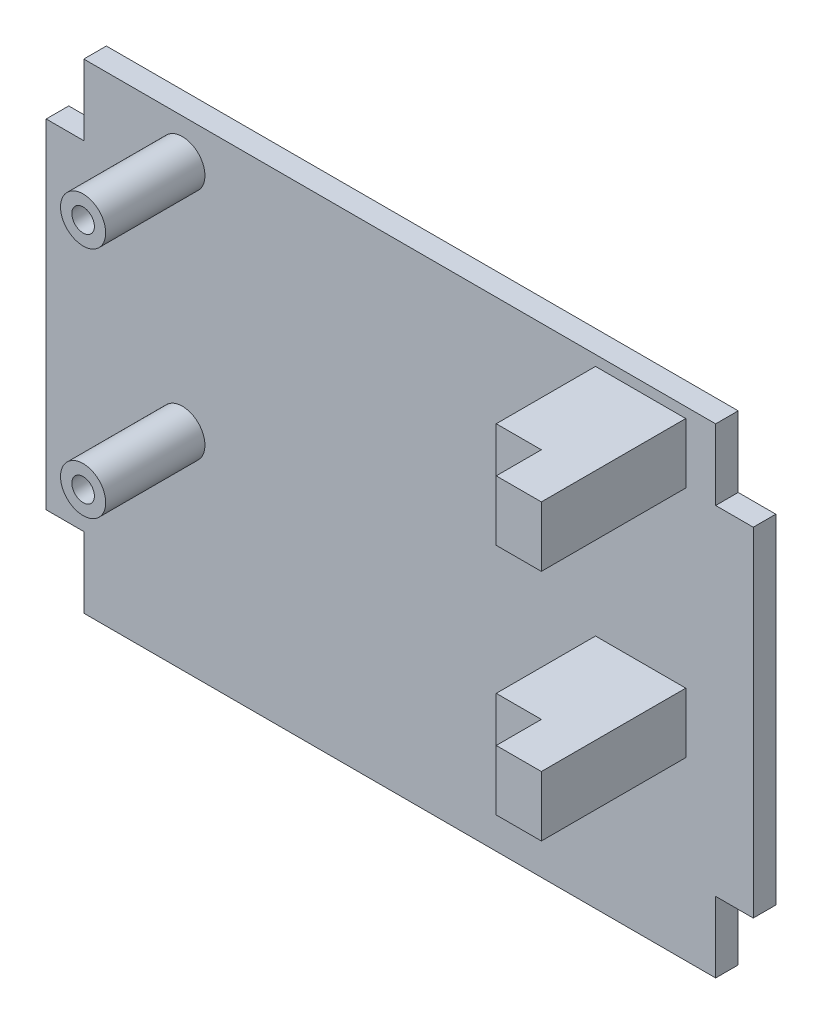
SolidWorks part; units mm, degrees
ref_plane "Plan de face" through (0, 0, 0) normal (0, 0, 1) x (1, 0, 0)
ref_plane "Plan de dessus" through (0, 0, 0) normal (0, 1, 0) x (1, 0, 0)
ref_plane "Plan de droite" through (0, 0, 0) normal (1, 0, 0) x (0, 0, -1)
sketch "Esquisse1" plane through (0, 0, 0) normal (0, 0, 1) x (1, 0, 0)
  line L1 (0, 0) -> (47, 0)
  line L2 (0, 0) -> (0, 31.9)
  line L3 (0, 31.9) -> (47, 31.9)
  line L4 (47, 0) -> (47, 31.9)
  dimension "D1" = 31.9
  dimension "D2" = 47
extrude "Boss.-Extru.1" add sketch "Esquisse1" along normal blind 1.5
sketch "Esquisse2" plane through (0, 0, 1.5) normal (0, 0, 1) x (1, 0, 0)
  line L0 (23.5, 31.9) -> (23.5, 0) construction
  line L1 (47, 31.9) -> (44.5, 31.9)
  line L2 (47, 31.9) -> (47, 27.2)
  line L3 (47, 27.2) -> (44.5, 27.2)
  line L4 (44.5, 31.9) -> (44.5, 27.2)
  line L5 (47, 31.9) -> (0, 31.9) construction
  line L6 (0, 0) -> (47, 0) construction
  line L8 (47, 15.95) -> (0, 15.95) construction
  line L9 (47, 0) -> (47, 31.9) construction
  line L10 (0, 31.9) -> (0, 0) construction
  line L11 (47, 4.7) -> (44.5, 4.7)
  line L12 (44.5, 0) -> (44.5, 4.7)
  line L13 (47, 0) -> (44.5, 0)
  line L14 (47, 0) -> (47, 4.7)
  line L15 (0, 0) -> (0, 4.7)
  line L16 (0, 0) -> (2.5, 0)
  line L17 (2.5, 0) -> (2.5, 4.7)
  line L18 (0, 4.7) -> (2.5, 4.7)
  line L19 (0, 27.2) -> (2.5, 27.2)
  line L20 (2.5, 31.9) -> (2.5, 27.2)
  line L21 (0, 31.9) -> (2.5, 31.9)
  line L22 (0, 31.9) -> (0, 27.2)
  dimension "D1" = 4.7
  dimension "D2" = 2.5
extrude "Enlèv. mat.-Extru.1" cut sketch "Esquisse2" against normal through all
sketch "Esquisse3" plane through (0, 0, 1.5) normal (0, 0, 1) x (1, 0, 0)
  line L0 (7.054, 31.2125) -> (39.514, 31.2125) construction
  line L1 (36.514, 31.2125) -> (42.514, 31.2125)
  line L2 (36.514, 31.2125) -> (36.514, 27.2125)
  line L3 (36.514, 27.2125) -> (42.514, 27.2125)
  line L4 (42.514, 31.2125) -> (42.514, 27.2125)
  line L5 (39.514, 11.6925) -> (39.514, 31.2125) construction
  line L6 (7.054, 21.4525) -> (39.514, 21.4525) construction
  line L7 (7.054, 31.2125) -> (7.054, 11.6925) construction
  line L8 (36.514, 15.6925) -> (42.514, 15.6925)
  line L9 (42.514, 11.6925) -> (42.514, 15.6925)
  line L10 (36.514, 11.6925) -> (42.514, 11.6925)
  line L11 (36.514, 11.6925) -> (36.514, 15.6925)
  circle A0 centre (9.054, 29.2125) radius 1.5
  circle A2 centre (9.054, 13.6925) radius 1.5
  dimension "D2" = 3
  dimension "D3" = 3
  dimension "D4" = 3
  dimension "D5" = 4
extrude "Boss.-Extru.2" add sketch "Esquisse3" along normal up to surface (6.5991 mm away)
sketch "Esquisse4" plane through (0, 0, 8.0991) normal (0, 0, 1) x (1, 0, 0)
  line L0 (42.514, 27.2125) -> (36.514, 27.2125) construction
  line L1 (42.514, 31.2125) -> (39.514, 31.2125)
  line L2 (42.514, 31.2125) -> (42.514, 27.2125)
  line L3 (42.514, 27.2125) -> (39.514, 27.2125)
  line L4 (39.514, 31.2125) -> (39.514, 27.2125)
  line L5 (36.514, 31.2125) -> (42.514, 31.2125) construction
  line L6 (7.054, 21.4525) -> (39.514, 21.4525) construction
  line L7 (7.054, 31.2125) -> (7.054, 11.6925) construction
  line L8 (39.514, 11.6925) -> (39.514, 31.2125) construction
  line L9 (42.514, 15.6925) -> (39.514, 15.6925)
  line L10 (39.514, 11.6925) -> (39.514, 15.6925)
  line L11 (42.514, 11.6925) -> (39.514, 11.6925)
  line L12 (42.514, 11.6925) -> (42.514, 15.6925)
  circle A0 centre (9.054, 29.2125) radius 0.75
  circle A1 centre (9.054, 13.6925) radius 0.75
  line M1 (36.514, 27.2125) -> (42.514, 27.2125)
  line M2 (42.514, 27.2125) -> (42.514, 31.2125)
  line M3 (42.514, 31.2125) -> (36.514, 31.2125)
  dimension "D1" = 1.5
extrude "Boss.-Extru.3" add sketch "Esquisse4" along normal blind 3 contours L4 M3 M1 M2 | L11 L12 L9 L10 region at (41.014, 29.2125, 8.0991) region at (41.014, 13.6925, 8.0991)
extrude "Enlèv. mat.-Extru.2" cut sketch "Esquisse4<3>" against normal blind 5 contours A0 | A1 region at (9.054, 29.2125, 8.0991) region at (9.054, 13.6925, 8.0991)
sketch "Esquisse4<3>" plane through (0, 0, 8.0991) normal (0, 0, 1) x (1, 0, 0) same geometry as "Esquisse4"
